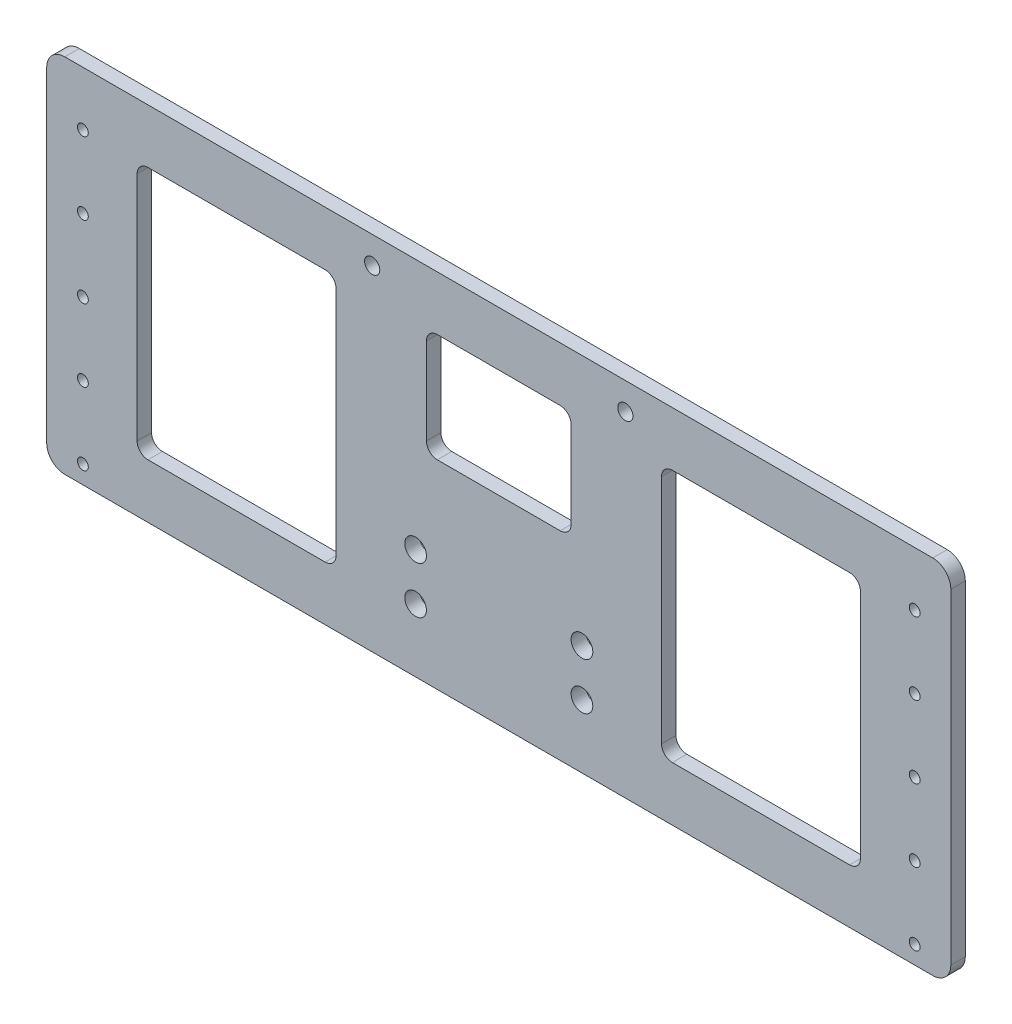
SolidWorks part; units mm, degrees
material "默认 (3)"
ref_plane "前视基准面" through (0, 0, 0) normal (0, 0, 1) x (1, 0, 0)
ref_plane "上视基准面" through (0, 0, 0) normal (0, 1, 0) x (1, 0, 0)
ref_plane "右视基准面" through (0, 0, 0) normal (1, 0, 0) x (0, 0, -1)
other "Configuration Table"
sketch "草图1" plane through (0, 0, 0) normal (0, 0, 1) x (1, 0, 0)
  line L0 (0, 0) -> (0, -50000) construction
  line L1 (-125, 15) -> (125, 15)
  line L2 (-125, 15) -> (-125, -15)
  line L3 (-125, -15) -> (125, -15)
  line L4 (125, 15) -> (125, -15)
  line L5 (-125, 15) -> (125, -15) construction
  line L6 (-125, -15) -> (125, 15) construction
  line L7 (-115, -10) -> (-115, 10) construction
  circle A0 centre (-115, -10) radius 1.5
  circle A1 centre (-115, 10) radius 1.5
  circle A2 centre (115, 10) radius 1.5
  circle A3 centre (115, -10) radius 1.5
  point P0 (0, 0)
  dimension "D6" = 5
  dimension "D7" = 3
  dimension "D1" = 250
  dimension "D2" = 30
  dimension "D4" = 20
  dimension "D5" = 10
  dimension "D3" = 2
extrude "凸台-拉伸1" add sketch "草图1" along normal blind 4
sketch "草图2" plane through (0, 0, 4) normal (0, 0, 1) x (1, 0, 0)
  line L0 (0, 0) -> (0, -50000) construction
  line L1 (0, 9) -> (50000, 9) construction
  line L2 (-23, 2.5) -> (23, 2.5) construction
  line L3 (-23, 2.5) -> (-23, 15.5) construction
  line L4 (-125, -15) -> (125, -15) construction
  circle A0 centre (-23, 2.5) radius 3
  circle A1 centre (23, 2.5) radius 3
  circle A2 centre (23, 15.5) radius 3
  circle A3 centre (-23, 15.5) radius 3
  dimension "D5" = 6
  dimension "D3" = 46
  dimension "D4" = 13
  dimension "D6" = 24
  dimension "D1" = 2
  dimension "D2" = 2
extrude "切除-拉伸1" cut sketch "草图2" against normal through all
sketch "草图3" plane through (0, 0, 4) normal (0, 0, 1) x (1, 0, 0)
  line L0 (0, 54.5) -> (0, -49945.5) construction
  line L1 (-125, 85) -> (125, 85)
  line L2 (-125, 85) -> (-125, 15)
  line L3 (-125, 15) -> (125, 15)
  line L4 (125, 85) -> (125, 15)
  line L5 (-125, 85) -> (125, 15) construction
  line L6 (-125, 15) -> (125, 85) construction
  line L8 (-115, 10) -> (-115, 30) construction
  circle A4 centre (-115, 10) radius 1.5 construction
  circle A5 centre (-115, 10) radius 1.5
  circle A6 centre (-115, 30) radius 1.5
  circle A7 centre (-115, 50) radius 1.5
  circle A8 centre (-115, 70) radius 1.5
  circle A9 centre (-115, 90) radius 1.5
  circle A10 centre (115, 10) radius 1.5
  circle A11 centre (115, 30) radius 1.5
  circle A12 centre (115, 50) radius 1.5
  circle A13 centre (115, 70) radius 1.5
  circle A14 centre (-35, 77.5) radius 2.1
  circle A15 centre (35, 77.5) radius 2.1
  point P0 (0, 50)
  line M16 (125, 15) -> (25.958, 15)
  dimension "D4" = 70
  dimension "D2" = 4.2
  dimension "D3" = 7.5
  dimension "D1" = 70
  dimension "D7" = 20
  dimension "D6" = 5
extrude "凸台-拉伸2" add sketch "草图3" against normal blind 4 contours L4 L1 L2 A12 A14 A6 A7 A8 A11 A13 M16 region at (0, 49.9563, 4)
sketch "草图4" plane through (0, 0, 4) normal (0, 0, 1) x (1, 0, 0)
  line L0 (0, 0) -> (0, -50000) construction
  line L1 (-125, 85) -> (125, 85) construction
  line L2 (-17, 70) -> (17, 70)
  line L3 (-20, 67) -> (-20, 43)
  line L4 (-17, 40) -> (17, 40)
  line L5 (20, 67) -> (20, 43)
  line L6 (-20, 70) -> (20, 40) construction
  line L7 (-20, 40) -> (20, 70) construction
  line L8 (-125, -15) -> (125, -15) construction
  line L9 (-97, 70) -> (-48, 70)
  line L10 (-100, 67) -> (-100, 3)
  line L11 (-97, 0) -> (-48, 0)
  line L12 (-45, 67) -> (-45, 3)
  line L13 (-100, 70) -> (-45, 0) construction
  line L14 (-100, 0) -> (-45, 70) construction
  line L15 (-125, 85) -> (-125, -15) construction
  line L16 (97, 0) -> (48, 0)
  line L17 (45, 67) -> (45, 3)
  line L18 (97, 70) -> (48, 70)
  line L19 (100, 67) -> (100, 3)
  arc A0 (17, 70) -> (20, 67) centre (17, 67) cw
  arc A1 (17, 40) -> (20, 43) centre (17, 43) ccw
  arc A2 (-20, 43) -> (-17, 40) centre (-17, 43) ccw
  arc A3 (-17, 70) -> (-20, 67) centre (-17, 67) ccw
  arc A4 (-48, 0) -> (-45, 3) centre (-48, 3) ccw
  arc A5 (-100, 3) -> (-97, 0) centre (-97, 3) ccw
  arc A6 (-48, 70) -> (-45, 67) centre (-48, 67) cw
  arc A7 (-97, 70) -> (-100, 67) centre (-97, 67) ccw
  arc A8 (48, 0) -> (45, 3) centre (48, 3) cw
  arc A9 (48, 70) -> (45, 67) centre (48, 67) ccw
  arc A10 (100, 3) -> (97, 0) centre (97, 3) cw
  arc A11 (97, 70) -> (100, 67) centre (97, 67) cw
  point P3 (0, 55)
  point P10 (-72.5, 35)
  dimension "D8" = 3
  dimension "D1" = 15
  dimension "D2" = 30
  dimension "D3" = 40
  dimension "D4" = 15
  dimension "D5" = 15
  dimension "D6" = 25
  dimension "D7" = 55
extrude "切除-拉伸2" cut sketch "草图4" against normal through all
fillet "圆角1" radius 5 4 edges at (125, -15, 2) (125, 85, 2) (-125, -15, 2) (-125, 85, 2)
sketch "草图5" plane through (0, 0, 4) normal (0, 0, 1) x (1, 0, 0)
  circle A0 centre (-23, 15.5) radius 3
  circle A1 centre (23, 15.5) radius 3
  dimension "D1" = 6
extrude "切除-拉伸3" cut sketch "草图5" against normal through all
